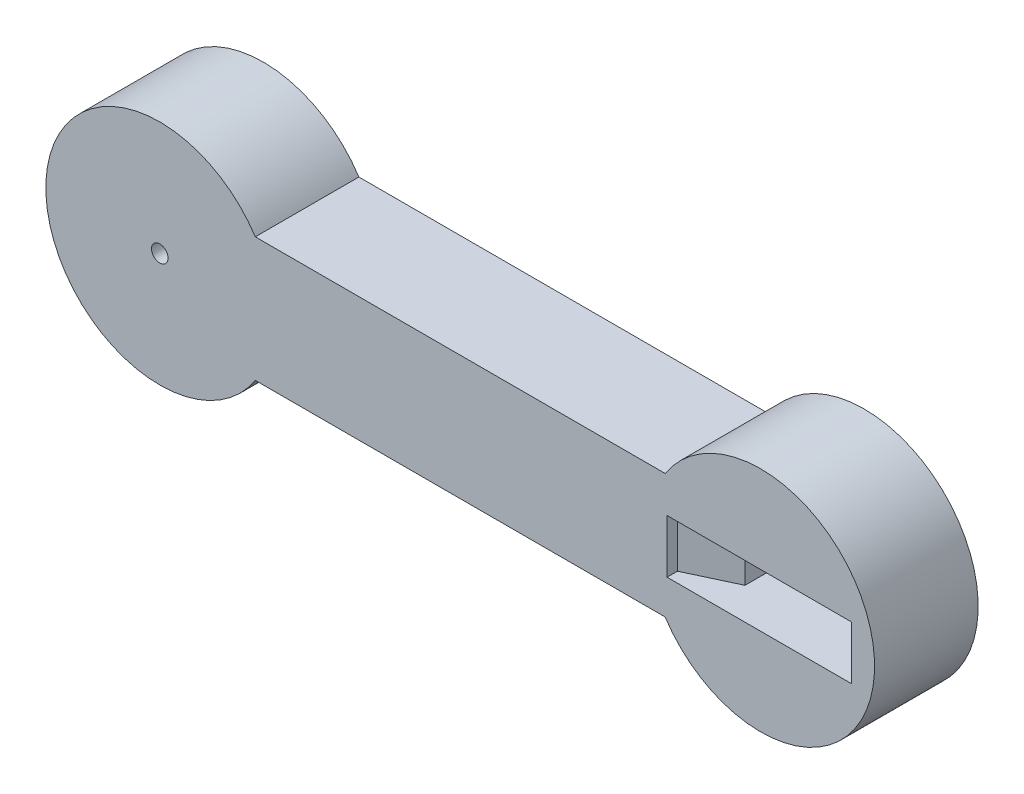
SolidWorks part; units mm, degrees
material "Custom Plastic"
ref_plane "Front Plane" through (0, 0, 0) normal (0, 0, 1) x (1, 0, 0)
ref_plane "Top Plane" through (0, 0, 0) normal (0, 1, 0) x (1, 0, 0)
ref_plane "Right Plane" through (0, 0, 0) normal (1, 0, 0) x (0, 0, -1)
sketch "Sketch1" plane through (0, 0, 0) normal (0, 0, 1) x (1, 0, 0)
  line L1 (0, 15) -> (145, 15)
  line L2 (0, 15) -> (0, -15)
  line L3 (0, -15) -> (145, -15)
  line L4 (145, 15) -> (145, -15)
  circle A0 centre (0, 0) radius 27.5
  circle A1 centre (145, 0) radius 27.5
  circle A2 centre (0, 0) radius 20
  point P9 (0, 0)
  dimension "D1" = 55
  dimension "D4" = 55
  dimension "D5" = 40
  dimension "D2" = 145
  dimension "D3" = 30
extrude "Boss-Extrude1" add sketch "Sketch1" along normal blind 25 contours L3 A1 L1 L4 | A1 L1 A0 L3 | L1 A1 L3 L4 | A2 L3 A0 L1 | A2 L1 A0 L3 | L3 A2 L1 L2 | L1 A2 L3 L2 region at (-6.7804, 0, 0) region at (9.0671, 0, 0) region at (-20.747, 0, 0) region at (21.8665, 0, 0) region at (72.5, 0, 0) region at (151.4116, 0, 0) region at (131.9332, 0, 0)
sketch "Sketch16" plane through (0, 0, 0) normal (0, 0, -1) x (-1, 0, 0)
  line L0 (-121.9511, -15) -> (-133.5193, -6.45) construction
  line L1 (-133.5193, -6.45) -> (-166.9193, -6.45)
  line L2 (-133.5193, -6.45) -> (-133.5193, 6.45)
  line L3 (-133.5193, 6.45) -> (-166.9193, 6.45)
  line L4 (-166.9193, -6.45) -> (-166.9193, 6.45)
  line L5 (-23.0489, -15) -> (-121.9511, -15) construction
  line L7 (-133.5193, 6.45) -> (-121.9511, 15) construction
  arc A1 (-121.9511, 15) -> (-121.9511, -15) centre (-145, 0) ccw construction
  dimension "D1" = 11.5682
  dimension "D2" = 33.4
  dimension "D3" = 12.9
extrude "Cut-Extrude10" cut sketch "Sketch16" against normal blind 4.5
ref_plane "Plane1" through (0, 0, 0) normal (0, -1, 0) x (-1, 0, 0)
sketch "Sketch19" plane through (0, 0, 0) normal (0, 0, -1) x (-1, 0, 0)
  circle A0 centre (0, 0) radius 20
extrude "Cut-Extrude14" cut sketch "Sketch19" against normal blind 5 contours A0
ref_plane "Plane2" through (0, 0, 6.5) normal (0, 0, -1) x (-1, 0, 0)
sketch "Sketch17" plane through (0, 0, 0) normal (0, 0, -1) x (-1, 0, 0)
  line L1 (-162.0193, 6.45) -> (-138.4193, 6.45)
  line L2 (-162.0193, 6.45) -> (-162.0193, -6.45)
  line L3 (-162.0193, -6.45) -> (-138.4193, -6.45)
  line L4 (-133.5193, -6.45) -> (-133.5193, 6.45)
  line L5 (-133.5193, 6.45) -> (-166.9193, 6.45)
  line L7 (-166.9193, -6.45) -> (-133.5193, -6.45)
  line L8 (-133.5193, -6.45) -> (-133.5193, 6.45)
  line L9 (-133.5193, 6.45) -> (-166.9193, 6.45)
  line L11 (-166.9193, -6.45) -> (-133.5193, -6.45)
  line L12 (-138.4193, 6.45) -> (-138.4193, -6.45)
  line L15 (-166.9193, 6.45) -> (-166.9193, -6.45)
  line L17 (-166.9193, 6.45) -> (-166.9193, -6.45)
  line M9 (-166.9193, 6.45) -> (-133.5193, 6.45)
  line M11 (-133.5193, -6.45) -> (-166.9193, -6.45)
  dimension "D2" = 4.9
  dimension "D3" = 4.9
  dimension "D1" = 0
extrude "Cut-Extrude11" cut sketch "Sketch17" against normal through all contours L12 L2 M9 M11 region at (150.2193, 0, 0)
sketch "Sketch18" plane through (0, 0, 0) normal (0, -1, 0) x (-1, 0, 0)
  line L0 (-138.4193, -25) -> (-138.4193, -15)
  line L6 (-122.4193, -25) -> (-122.4193, -22.5)
  line L8 (-166.9193, -4.5) -> (-162.0193, -4.5)
  line L9 (-166.9193, 0) -> (-166.9193, -4.5)
  line L11 (-166.9193, 0) -> (-166.9193, -4.5)
  line L13 (-133.5193, -4.5) -> (-133.5193, 0)
  line L14 (-133.5193, 0) -> (-166.9193, 0)
  line L16 (-166.9193, -4.5) -> (-162.0193, -4.5)
  line L21 (-133.5193, -4.5) -> (-133.5193, 0)
  line L22 (-133.5193, 0) -> (-166.9193, 0)
  line L26 (-122.4193, -22.5) -> (-138.4193, -15)
  line L28 (-23.0489, -25) -> (-121.9511, -25) construction
  line L30 (-138.4193, -25) -> (-122.4193, -25)
  line L31 (-138.4193, -15) -> (-138.4193, -25)
  line L34 (-162.0193, -25) -> (-138.4193, -25)
  line L35 (-162.0193, -25) -> (-138.4193, -25)
  line L36 (-138.4193, -25) -> (-138.4193, -4.5)
  line L37 (-138.4193, -25) -> (-138.4193, -4.5)
  line L38 (-162.0193, -4.5) -> (-162.0193, -25)
  line L40 (-162.0193, -4.5) -> (-162.0193, -25)
  line L42 (-138.4193, -4.5) -> (-133.5193, -4.5)
  line L43 (-138.4193, -4.5) -> (-133.5193, -4.5)
  dimension "D2" = 15
  dimension "D3" = 16
  dimension "D4" = 2.5
  dimension "D1" = 0
extrude "Cut-Extrude13" cut sketch "Sketch18" against normal mid plane 12.9 contours L0 region at (132.0193, 0, 21.5)
sketch "Sketch20" plane through (0, 0, 6.5) normal (0, 0, -1) x (-1, 0, 0)
  line L0 (-133.5193, 6.45) -> (-166.9193, 6.45) construction
  line L1 (-166.9193, 6.45) -> (-133.5193, 6.45)
  line L2 (-166.9193, 6.45) -> (-166.9193, -6.45)
  line L3 (-166.9193, -6.45) -> (-133.5193, -6.45)
  line L4 (-133.5193, 6.45) -> (-133.5193, -6.45)
  line L5 (-166.9193, 6.45) -> (-166.9193, -6.45) construction
  line L6 (-166.9193, -6.45) -> (-133.5193, -6.45) construction
  dimension "D1" = 33.4
extrude "Cut-Extrude15" cut sketch "Sketch20" against normal through all
sketch "Sketch21" plane through (0, 0, 0) normal (0, 0, -1) x (-1, 0, 0)
  circle A0 centre (-136.75, 0) radius 1.1
  circle A1 centre (-163.75, 0) radius 1.1
  dimension "D3" = 2.2
  dimension "D1" = 14.7989
  dimension "D2" = 27
extrude "Cut-Extrude16" cut sketch "Sketch21" against normal through all contours A1 | A0 region at (136.75, 0, 0) region at (163.75, 0, 0)
ref_axis "Axis1" through (136.75, 0, 34.2314) along (0, 0, -1)
sketch "Sketch22" plane through (0, 0, 25) normal (0, 0, 1) x (1, 0, 0)
  circle A0 centre (0, 0) radius 2
  arc A1 (23.0489, 15) -> (23.0489, -15) centre (0, 0) ccw construction
  dimension "D1" = 4
extrude "Cut-Extrude17" cut sketch "Sketch22" against normal up to surface (20 mm away) contours A0 region at (0, 0, 25) up to face at (-20, 0, 5)
